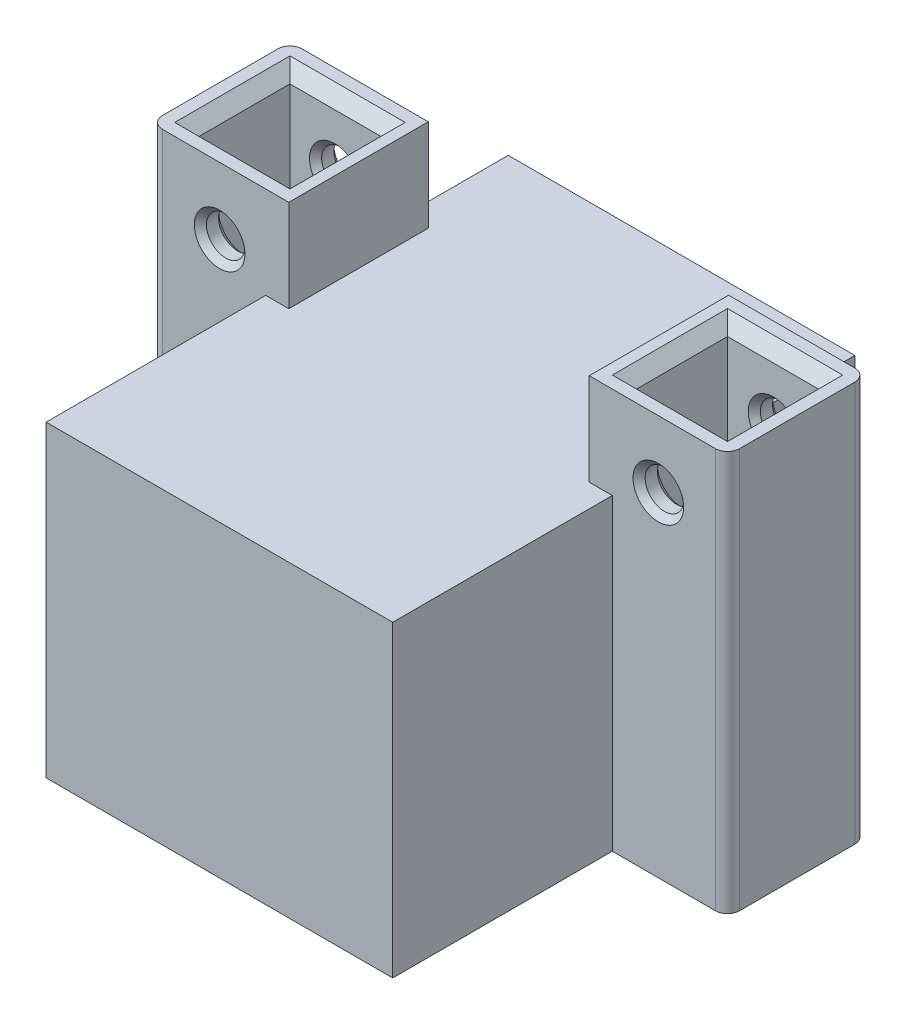
SolidWorks part; units mm, degrees
ref_plane "Front Plane" through (0, 0, 0) normal (0, 0, 1) x (1, 0, 0)
ref_plane "Top Plane" through (0, 0, 0) normal (0, 1, 0) x (1, 0, 0)
ref_plane "Right Plane" through (0, 0, 0) normal (1, 0, 0) x (0, 0, -1)
sketch "Sketch3" plane through (0, 0, 0) normal (0, 1, 0) x (-1, 0, 0)
  line L1 (0, 0) -> (57.15, 0)
  line L2 (0, 0) -> (0, 76.2)
  line L3 (0, 76.2) -> (57.15, 76.2)
  line L4 (57.15, 0) -> (57.15, 76.2)
  dimension "D1" = 76.2
  dimension "D2" = 57.15
extrude "Boss-Extrude2" add sketch "Sketch3" against normal blind 50.8
sketch "Sketch4" plane through (0, -50.8, 0) normal (0, -1, 0) x (1, 0, 0)
  line L1 (-3.81, 72.39) -> (-53.34, 72.39)
  line L2 (-3.81, 72.39) -> (-3.81, 3.81)
  line L3 (-3.81, 3.81) -> (-53.34, 3.81)
  line L4 (-53.34, 72.39) -> (-53.34, 3.81)
  line L8 (-57.15, 76.2) -> (0, 76.2) construction
  line L9 (0, 0) -> (-57.15, 0) construction
  line L10 (0, 76.2) -> (0, 0) construction
  line L11 (-57.15, 0) -> (-57.15, 76.2) construction
  dimension "D1" = 3.81
  dimension "D2" = 3.81
  dimension "D3" = 3.81
  dimension "D4" = 3.81
extrude "Cut-Extrude2" cut sketch "Sketch4" against normal blind 44.45
sketch "Sketch5" plane through (-57.15, 0, 0) normal (1, 0, 0) x (0, 0, -1)
  line L1 (-14.478, -46.99) -> (-5.08, -46.99)
  line L2 (-14.478, -46.99) -> (-14.478, -35.56)
  line L3 (-14.478, -35.56) -> (-5.08, -35.56)
  line L4 (-5.08, -46.99) -> (-5.08, -35.56)
  line L6 (0, -50.8) -> (0, 0) construction
  line L7 (0, -50.8) -> (-76.2, -50.8) construction
  dimension "D1" = 5.08
  dimension "D2" = 3.81
  dimension "D3" = 11.43
  dimension "D4" = 9.398
extrude "Cut-Extrude3" cut sketch "Sketch5" along normal up to next
sketch "Sketch6" plane through (-57.15, 0, 0) normal (-1, 0, 0) x (0, 0, 1)
  line L0 (46.54, 0) -> (46.54, 36.83)
  line L1 (46.54, 36.83) -> (0, 36.83)
  line L2 (0, 36.83) -> (0, 34.29)
  line L3 (0, 34.29) -> (44, 34.29)
  line L4 (44, 34.29) -> (44, 0)
  line L5 (0, 0) -> (76.2, 0) construction
  line L6 (44, 0) -> (46.54, 0)
  line L7 (0, -50.8) -> (0, 0) construction
  dimension "D1" = 44
  dimension "D2" = 34.29
  dimension "D3" = 2.54
  dimension "D4" = 2.54
extrude "Motor Mounting Shape" add sketch "Sketch6" against normal up to surface (57.15 mm away) up to face at (0, -25.4, 38.1)
sketch "Sketch8" plane through (0, 36.83, 0) normal (0, 1, 0) x (1, 0, 0)
  line L0 (-44.075, -38.77) -> (-13.075, -7.77) construction
  line L1 (-13.075, -38.77) -> (-44.075, -7.77) construction
  line L2 (-44.075, -38.77) -> (-44.075, -7.77) construction
  line L3 (-44.075, -7.77) -> (-13.075, -7.77) construction
  line L4 (-28.575, -46.54) -> (-28.575, 0) construction
  line L5 (0, -46.54) -> (-57.15, -46.54) construction
  line L6 (0, 0) -> (-57.15, 0) construction
  line L7 (-37.465, 0) -> (-19.685, 0)
  line L8 (-19.685, 0) -> (-19.685, -23.27)
  line L9 (-37.465, -23.27) -> (-37.465, 0)
  circle A1 centre (-44.075, -7.77) radius 1.6
  circle A2 centre (-13.075, -7.77) radius 1.6
  circle A3 centre (-13.075, -38.77) radius 1.6
  circle A4 centre (-44.075, -38.77) radius 1.6
  arc A6 (-37.465, -23.27) -> (-19.685, -23.27) centre (-28.575, -23.27) ccw
  point P10 (-28.575, -23.27)
  dimension "D2" = 3.2
  dimension "D3" = 8.89
  dimension "D1" = 31
extrude "Motor-Mounting-Holes" cut sketch "Sketch8" against normal up to next
sketch "Sketch7" plane through (0, 0, 0) normal (0, 1, 0) x (1, 0, 0)
  line L0 (-46.355, -76.2) -> (-46.355, -46.54)
  line L1 (-57.15, -76.2) -> (0, -76.2) construction
  line L2 (-46.355, -46.54) -> (-38.735, -46.54)
  line L3 (-38.735, -46.54) -> (-38.735, -76.2)
  line L4 (-38.735, -76.2) -> (-46.355, -76.2)
  line L5 (-18.415, -76.2) -> (-10.795, -76.2)
  line L6 (-10.795, -76.2) -> (-10.795, -46.54)
  line L7 (-10.795, -46.54) -> (-18.415, -46.54)
  line L8 (-18.415, -46.54) -> (-18.415, -76.2)
  line L9 (-46.355, -76.2) -> (-57.15, -76.2) construction
  line L10 (-38.735, -76.2) -> (-18.415, -76.2) construction
  line L11 (-10.795, -76.2) -> (0, -76.2) construction
  line L12 (0, -46.54) -> (-57.15, -46.54) construction
  dimension "D1" = 7.62
  dimension "D2" = 20.32
extrude "Tray Support Mounting Shape" add sketch "Sketch7" along normal blind 44.45
sketch "Sketch9" plane through (0, -50.8, 0) normal (0, -1, 0) x (1, 0, 0)
  line L0 (0, 40) -> (-3.81, 40)
  line L1 (0, 17) -> (19, 17)
  line L2 (0, 21) -> (0, 36)
  line L3 (0, 40) -> (19, 40)
  line L5 (19, 40) -> (19, 17)
  line L6 (0, 36) -> (15, 36)
  line L7 (15, 36) -> (15, 21)
  line L8 (15, 21) -> (0, 21)
  line L9 (-3.81, 3.81) -> (-3.81, 72.39) construction
  line L10 (-3.81, 40) -> (-3.81, 17)
  line L11 (-28.575, 76.2) -> (-28.575, 0) construction
  line L12 (-3.81, 17) -> (0, 17)
  line L13 (0, 36) -> (0, 21)
  line L14 (0, 0) -> (-57.15, 0) construction
  line L15 (-57.15, 76.2) -> (0, 76.2) construction
  line L16 (-72.15, 36) -> (-72.15, 21)
  line L17 (-72.15, 21) -> (-57.15, 21)
  line L18 (-57.15, 21) -> (-57.15, 36)
  line L19 (-57.15, 36) -> (-72.15, 36)
  line L20 (-53.34, 17) -> (-57.15, 17)
  line L21 (-53.34, 40) -> (-53.34, 17)
  line L22 (-57.15, 40) -> (-53.34, 40)
  line L23 (-57.15, 40) -> (-76.15, 40)
  line L24 (-76.15, 40) -> (-76.15, 17)
  line L25 (-57.15, 17) -> (-76.15, 17)
  dimension "D1" = 4
  dimension "D2" = 4
  dimension "D3" = 4
  dimension "D4" = 15
  dimension "D5" = 3.81
  dimension "D6" = 3.81
  dimension "D7" = 17
extrude "Boss-Extrude3" add sketch "Sketch9" against normal blind 66 contours L1 L5 L3 L0 L10 L12 | L13 L8 L7 L6 | L20 L25 L24 L23 L22 L21 | L16 L17 L18 L19
sketch "Sketch10" plane through (-76.15, 0, 0) normal (-1, 0, 0) x (0, 0, 1)
  line L1 (17, 15.2) -> (40, 15.2) construction
  line L2 (40, -50.8) -> (17, -50.8) construction
  circle A0 centre (28.5, 4.2) radius 3.175
  point P2 (28.5, 15.2)
  dimension "D1" = 6.35
  dimension "D2" = 55
chamfer "Chamfer1" distance 2 angle 45 8 edges at (-57.15, 15.2, 28.5) (-64.65, 15.2, 21) (-72.15, 15.2, 28.5) (-64.65, 15.2, 36) (7.5, 15.2, 21) (0, 15.2, 28.5) (15, 15.2, 28.5) (7.5, 15.2, 36)
fillet "Fillet1" radius 2 4 edges at (-76.15, -17.8, 40) (-76.15, -17.8, 17) (19, -17.8, 40) (19, -17.8, 17)
sketch "Sketch11" plane through (0, 0, 0) normal (1, 0, 0) x (0, 0, -1)
  line L0 (-44, 0) -> (-44, 34.29)
  line L1 (-44, 34.29) -> (0, 34.29)
  line L2 (0, 34.29) -> (0, 51.5993)
  line L3 (0, 51.5993) -> (-81.1962, 51.5993)
  line L4 (-81.1962, 51.5993) -> (-81.1962, 0)
  line L5 (-81.1962, 0) -> (-44, 0)
extrude "Cut-Extrude5" cut sketch "Sketch11" against normal through all
sketch "Sketch12" plane through (0, 0, 40) normal (0, 0, 1) x (1, 0, 0)
  line L0 (17, -50.8) -> (0, -50.8) construction
  line L1 (-3.81, 7.6) -> (19, 7.6) construction
  line L2 (-3.81, 15.2) -> (-3.81, 0) construction
  line L3 (19, 15.2) -> (19, -50.8) construction
  line L4 (-53.34, 9.9356) -> (-76.15, 9.9356) construction
  line L5 (-53.34, 15.2) -> (-53.34, 0) construction
  line L6 (-76.15, -50.8) -> (-76.15, 15.2) construction
  circle A0 centre (7.595, 4.2) radius 3.175
  circle A1 centre (-64.745, 4.2) radius 3.175
  point P10 (7.595, 7.6)
  point P19 (-64.745, 9.9356)
  dimension "D1" = 6.35
  dimension "D3" = 6.35
  dimension "D2" = 55
extrude "Cut-Extrude6" cut sketch "Sketch12" against normal through all
chamfer "Chamfer2" distance 1 angle 45 8 edges at (10.77, 4.2, 40) (4.42, 4.2, 36) (10.77, 4.2, 21) (4.42, 4.2, 17) (-61.57, 4.2, 17) (-67.92, 4.2, 21) (-61.57, 4.2, 36) (-61.57, 4.2, 40)
